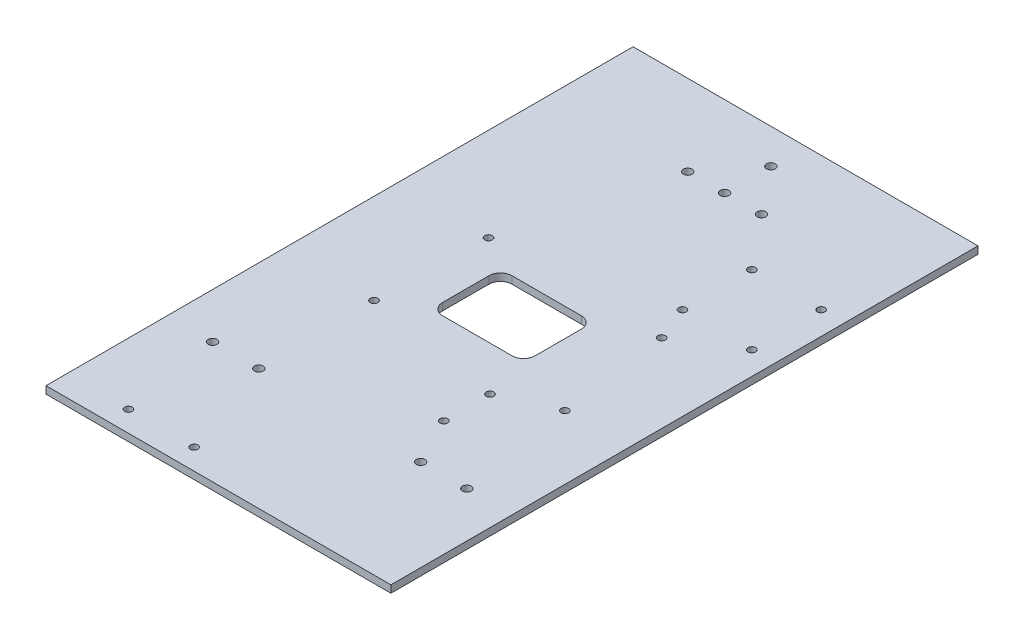
SolidWorks part; units mm, degrees
ref_plane "Front Plane" through (0, 0, 0) normal (0, 0, 1) x (1, 0, 0)
ref_plane "Top Plane" through (0, 0, 0) normal (0, 1, 0) x (1, 0, 0)
ref_plane "Right Plane" through (0, 0, 0) normal (1, 0, 0) x (0, 0, -1)
sketch "Sketch1" plane through (0, 0, 0) normal (0, 1, 0) x (1, 0, 0)
  line L1 (-74.6125, -127) -> (74.6125, -127)
  line L2 (-74.6125, -127) -> (-74.6125, 127)
  line L3 (-74.6125, 127) -> (74.6125, 127)
  line L4 (74.6125, -127) -> (74.6125, 127)
  line L5 (-74.6125, -127) -> (74.6125, 127) construction
  line L6 (-74.6125, 127) -> (74.6125, -127) construction
  point P0 (0, 0)
  dimension "D1" = 254
  dimension "D2" = 149.225
extrude "Boss-Extrude1" add sketch "Sketch1" along normal blind 3.175
hole_wizard "#6 Clearance Hole1" positions "Sketch8" profile "Sketch7" hole size "#6" standard "ANSI Inch" end condition through all
sketch "Sketch8" plane through (0, 3.175, 0) normal (0, 1, 0) x (1, 0, 0)
  line L1 (74.6125, 127) -> (-74.6125, 127) construction
  line L3 (0, 145.0259) -> (0, -144.5666) construction
  line L5 (-74.6125, -127) -> (74.6125, -127) construction
  point P0 (0, 112)
  point P2 (0, 92)
  point P15 (35, -74.54)
  point P17 (55, -74.54)
  point P19 (-35, -74.54)
  point P21 (-55, -74.54)
  point P31 (-15.965, 92)
  point P33 (15.965, 92)
  dimension "D2" = 15
  dimension "D3" = 20
  dimension "D6" = 70
  dimension "D7" = 35
  dimension "D8" = 20
  dimension "D9" = 20
  dimension "D10" = 52.46
  dimension "D11" = 15.965
  dimension "D12" = 31.93
  dimension "D13" = 35
sketch "Sketch7" plane through (0, 3.175, -112) normal (1, 0, 0) x (0, 0, 1)
  line L0 (0, 0) -> (0, 3.175)
  line L1 (0, 3.175) -> (1.8986, 3.175)
  line L2 (1.8986, 3.175) -> (1.8986, 0)
  line L5 (1.8986, 0) -> (0, 0)
  line L11 (0, -6.35) -> (0, 107.95) construction
  dimension "Thru Hole Dia." = 3.7973
  dimension "Thru Hole Depth" = 3.175
hole_wizard "#4 Clearance Hole1" positions "Sketch10" profile "Sketch9" hole size "#4" standard "ANSI Inch" end condition through all
sketch "Sketch10" plane through (0, 3.175, 0) normal (0, 1, 0) x (1, 0, 0)
  line L0 (0, -127) -> (0, 0) construction
  line L1 (-74.6125, -127) -> (74.6125, -127) construction
  line L2 (74.6125, -127) -> (74.6125, 127) construction
  point P2 (-47.95, -118)
  point P13 (-19.54, -118)
  point P14 (46.99, -24.13)
  point P16 (-35.56, -24.13)
  point P18 (40.64, 24.13)
  point P20 (-34.29, 24.13)
  point P22 (64.6125, 39.13)
  point P24 (34.6125, 39.13)
  point P26 (64.6125, 69.13)
  point P28 (34.6125, 69.13)
  point P31 (24.6125, -54.13)
  point P33 (24.6125, -34.13)
  dimension "D1" = 47.95
  dimension "D2" = 28.41
  dimension "D3" = 9
  dimension "D4" = 34.29
  dimension "D5" = 81.28
  dimension "D6" = 24.13
  dimension "D7" = 1.27
  dimension "D8" = 6.35
  dimension "D9" = 48.26
  dimension "D10" = 10
  dimension "D11" = 30
  dimension "D12" = 30
  dimension "D13" = 15
  dimension "D14" = 20
  dimension "D15" = 50
  dimension "D16" = 10
sketch "Sketch9" plane through (-47.95, 3.175, 118) normal (1, 0, 0) x (0, 0, 1)
  line L0 (0, 0) -> (0, 3.175)
  line L1 (0, 3.175) -> (1.6319, 3.175)
  line L2 (1.6319, 3.175) -> (1.6319, 0)
  line L5 (1.6319, 0) -> (0, 0)
  line L11 (0, -6.35) -> (0, 107.95) construction
  dimension "Thru Hole Dia." = 3.2639
  dimension "Thru Hole Depth" = 3.175
sketch "Sketch11" plane through (0, 3.175, 0) normal (0, 1, 0) x (1, 0, 0)
  line L1 (20, -15) -> (-20, -15)
  line L2 (20, -15) -> (20, 15)
  line L3 (20, 15) -> (-20, 15)
  line L4 (-20, -15) -> (-20, 15)
  line L5 (20, -15) -> (-20, 15) construction
  line L6 (20, 15) -> (-20, -15) construction
  point P0 (0, 0)
  dimension "D1" = 30
  dimension "D2" = 40
extrude "Cut-Extrude1" cut sketch "Sketch11" against normal up to surface (3.175 mm away) up to face at (-47.95, 0, 119.632)
fillet "Fillet1" radius 5 4 edges at (-20, 1.5875, -15) (20, 1.5875, -15) (20, 1.5875, 15) (-20, 1.5875, 15)
